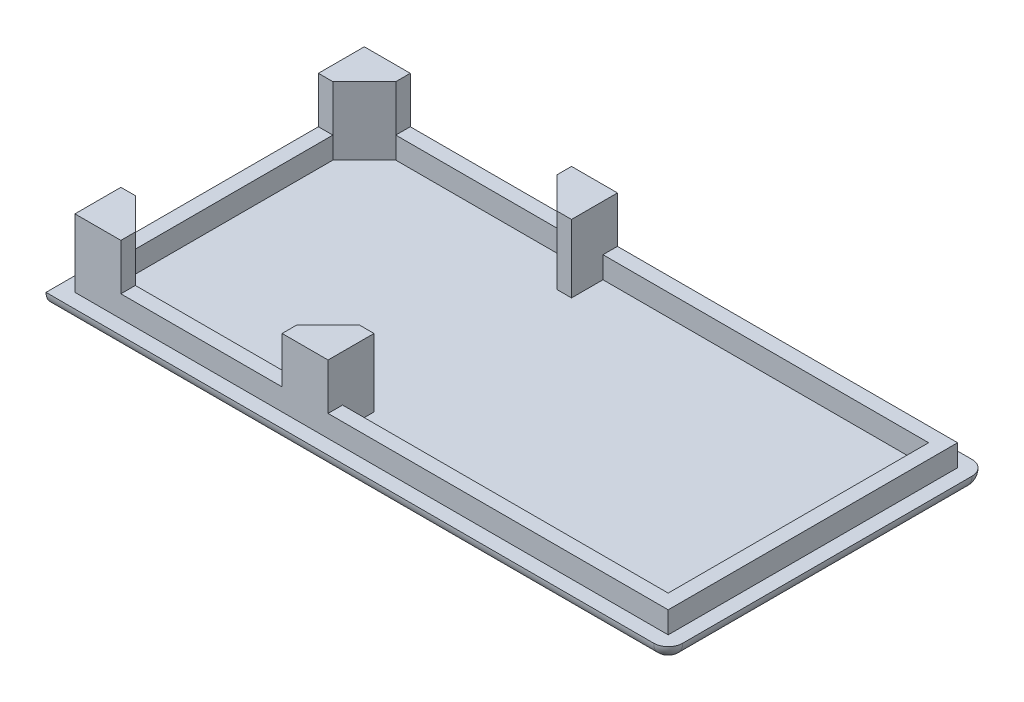
SolidWorks part; units mm, degrees
ref_plane "Front Plane" through (0, 0, 0) normal (0, 0, 1) x (1, 0, 0)
ref_plane "Top Plane" through (0, 0, 0) normal (0, 1, 0) x (1, 0, 0)
ref_plane "Right Plane" through (0, 0, 0) normal (1, 0, 0) x (0, 0, -1)
sketch "Sketch1" plane through (0, 0, 0) normal (0, 0, 1) x (1, 0, 0)
  line L1 (0, 0) -> (43, 0)
  line L2 (0, 0) -> (0, 1)
  line L3 (0, 1) -> (43, 1)
  line L4 (43, 0) -> (43, 1)
  dimension "D1" = 1
  dimension "D2" = 43
extrude "Boss-Extrude1" add sketch "Sketch1" along normal blind 22
fillet "Fillet1" radius 1 3 edges at (43, 0, 11) (21.5, 0, 0) (21.5, 0, 22)
sketch "Sketch2" plane through (0, 1, 0) normal (0, 1, 0) x (1, 0, 0)
  line L0 (2, -2) -> (2, -20)
  line L1 (1, -1) -> (42, -1)
  line L2 (1, -1) -> (1, -21)
  line L3 (1, -21) -> (42, -21)
  line L4 (42, -1) -> (42, -21)
  line L5 (2, -20) -> (41, -20)
  line L6 (41, -2) -> (41, -20)
  line L7 (2, -2) -> (41, -2)
  line L9 (43, -21) -> (43, -1) construction
  line L10 (0, -22) -> (42, -22) construction
  dimension "D2" = 20
  dimension "D3" = 1
  dimension "D4" = 1
  dimension "D5" = 41
  dimension "D1" = 1
extrude "Boss-Extrude2" add sketch "Sketch2" along normal blind 1.5
sketch "Sketch3" plane through (0, 2.5, 0) normal (0, 1, 0) x (1, 0, 0)
  line L0 (1, -21) -> (4.175, -21)
  line L1 (1, -21) -> (42, -21) construction
  line L2 (4.175, -21) -> (4.175, -20)
  line L3 (2, -20) -> (41, -20) construction
  line L4 (4.175, -20) -> (2, -20) construction
  line L5 (2, -20) -> (2, -17.825) construction
  line L6 (2, -2) -> (2, -20) construction
  line L7 (2, -17.825) -> (1, -17.825)
  line L8 (1, -1) -> (1, -21) construction
  line L9 (1, -17.825) -> (1, -21)
  line L10 (4.175, -20) -> (2, -17.825)
  line L11 (1, -1) -> (1, -4.175)
  line L12 (1, -4.175) -> (2, -4.175)
  line L13 (2, -4.175) -> (4.175, -2)
  line L14 (41, -2) -> (2, -2) construction
  line L15 (4.175, -2) -> (4.175, -1)
  line L16 (42, -1) -> (1, -1) construction
  line L17 (4.175, -1) -> (1, -1)
  line L18 (18.494, -21) -> (18.494, -17.825)
  line L19 (18.494, -9) -> (18.494, -21) construction
  line L20 (18.494, -17.825) -> (17.494, -17.825)
  line L22 (17.494, -21) -> (17.494, -8) construction
  line L24 (17.494, -17.825) -> (15.319, -20)
  line L25 (15.319, -20) -> (15.319, -21)
  line L26 (15.319, -21) -> (18.494, -21)
  line L27 (18.494, -1) -> (18.494, -4.175)
  line L28 (18.494, -4.175) -> (17.494, -4.175)
  line L29 (17.494, -4.175) -> (15.319, -2)
  line L30 (15.319, -2) -> (15.319, -1)
  line L31 (15.319, -1) -> (18.494, -1)
  dimension "D1" = 3.175
  dimension "D2" = 3.175
  dimension "D3" = 3.175
  dimension "D4" = 3.175
  dimension "D5" = 3.175
  dimension "D6" = 3.175
  dimension "D7" = 3.175
  dimension "D8" = 3.175
  dimension "D9" = 1
extrude "Boss-Extrude3" add sketch "Sketch3" along normal blind 3.199 and the other way blind 1.5
